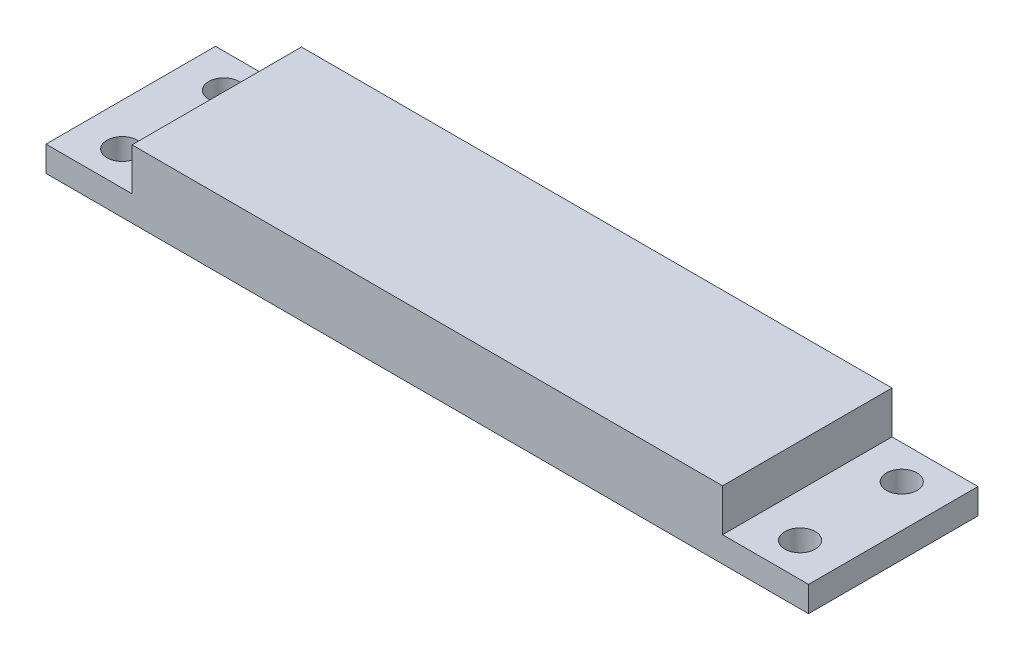
SolidWorks part; units mm, degrees
ref_plane "Front Plane" through (0, 0, 0) normal (0, 0, 1) x (1, 0, 0)
ref_plane "Top Plane" through (0, 0, 0) normal (0, 1, 0) x (1, 0, 0)
ref_plane "Right Plane" through (0, 0, 0) normal (1, 0, 0) x (0, 0, -1)
sketch "Sketch1" plane through (0, 0, 0) normal (0, 1, 0) x (1, 0, 0)
  line L1 (34.85, -10) -> (-34.85, -10)
  line L2 (34.85, -10) -> (34.85, 10)
  line L3 (34.85, 10) -> (-34.85, 10)
  line L4 (-34.85, -10) -> (-34.85, 10)
  line L5 (34.85, -10) -> (-34.85, 10) construction
  line L6 (34.85, 10) -> (-34.85, -10) construction
  line L7 (45, -10) -> (-45, -10)
  line L8 (45, -10) -> (45, 10)
  line L9 (45, 10) -> (-45, 10)
  line L10 (-45, -10) -> (-45, 10)
  line L11 (45, -10) -> (-45, 10) construction
  line L12 (45, 10) -> (-45, -10) construction
  point P0 (0, 0)
  point P6 (0, 0)
  dimension "D1" = 69.7
  dimension "D2" = 90
  dimension "D3" = 20
extrude "Boss-Extrude1" add sketch "Sketch1" along normal blind 3 contours L10 L7 L4 L9 | L4 L1 L2 L3 | L8 L9 L2 L7 region at (0, 0, 0) region at (39.925, 0, 0) region at (-39.925, 0, 0)
extrude "Boss-Extrude2" add sketch "Sketch1<3>" along normal blind 8 contours L4 L1 L2 L3 region at (0, 0, 0)
sketch "Sketch1<3>" plane through (0, 0, 0) normal (0, 1, 0) x (1, 0, 0) same geometry as "Sketch1"
sketch "Sketch4" plane through (0, 3, 0) normal (0, 1, 0) x (1, 0, 0)
  line L0 (-45, -10) -> (-45, 10) construction
  line L1 (45, -10) -> (45, 10) construction
  line L2 (45, 10) -> (34.85, 10) construction
  line L3 (-34.85, 10) -> (-45, 10) construction
  line L4 (-34.85, -10) -> (-45, -10) construction
  line L5 (45, -10) -> (34.85, -10) construction
  point P0 (-40, 6)
  point P2 (-40, -6)
  point P4 (40, -6)
  point P6 (40, 6)
  dimension "D1" = 5
  dimension "D2" = 5
  dimension "D3" = 4
  dimension "D4" = 4
  dimension "D5" = 4
  dimension "D6" = 4
hole_wizard "M3 Clearance Hole1" positions "Sketch4" profile "Sketch5" hole size "M3" standard "ANSI Metric"
sketch "Sketch5" plane through (-40, 3, -6) normal (1, 0, 0) x (0, 0, 1)
  line L0 (0, 0) -> (0, 11.0815)
  line L1 (0, 11.0815) -> (1.8, 10)
  line L2 (1.8, 10) -> (1.8, 0)
  line L5 (1.8, 0) -> (0, 0)
  line L10 (0, 11.0815) -> (-1.8, 10) construction
  line L11 (0, -6.35) -> (0, 107.95) construction
  dimension "Hole Dia." = 3.6
  dimension "Hole Depth" = 10
  dimension "Drill Angle" = 118
